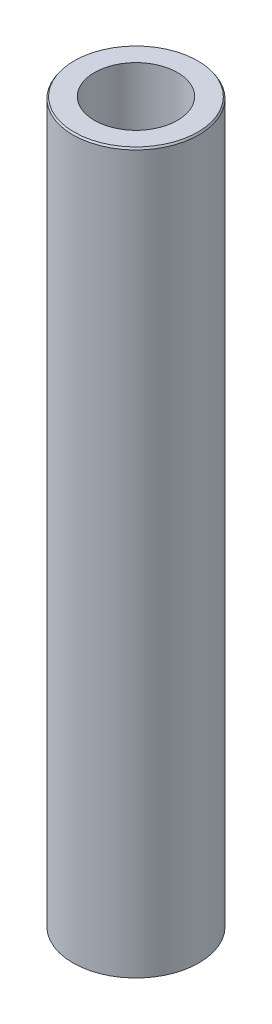
SolidWorks part; units mm, degrees
ref_plane "Front Plane" through (0, 0, 0) normal (0, 0, 1) x (1, 0, 0)
ref_plane "Top Plane" through (0, 0, 0) normal (0, 1, 0) x (1, 0, 0)
ref_plane "Right Plane" through (0, 0, 0) normal (1, 0, 0) x (0, 0, -1)
sketch "Sketch1" plane through (0, 0, 0) normal (0, 1, 0) x (1, 0, 0)
  circle A0 centre (0, 0) radius 52.5
  dimension "SHAFT_OD" = 105
extrude "Boss-Extrude1" add sketch "Sketch1" along normal blind 600
sketch "Sketch2" plane through (0, 0, 0) normal (0, 1, 0) x (1, 0, 0)
  circle A0 centre (0, 0) radius 34.5818
  dimension "BORE_D" = 69.1635
extrude "Cut-Extrude1" cut sketch "Sketch2" along normal through all
chamfer "Chamfer1" distance 1.4884 angle 33.896 2 edges at (0, 600, 52.5) (0, 0, 52.5) first distance on face at (0, 600, 52.5) first distance on face at (0, 0, 34.5818)
